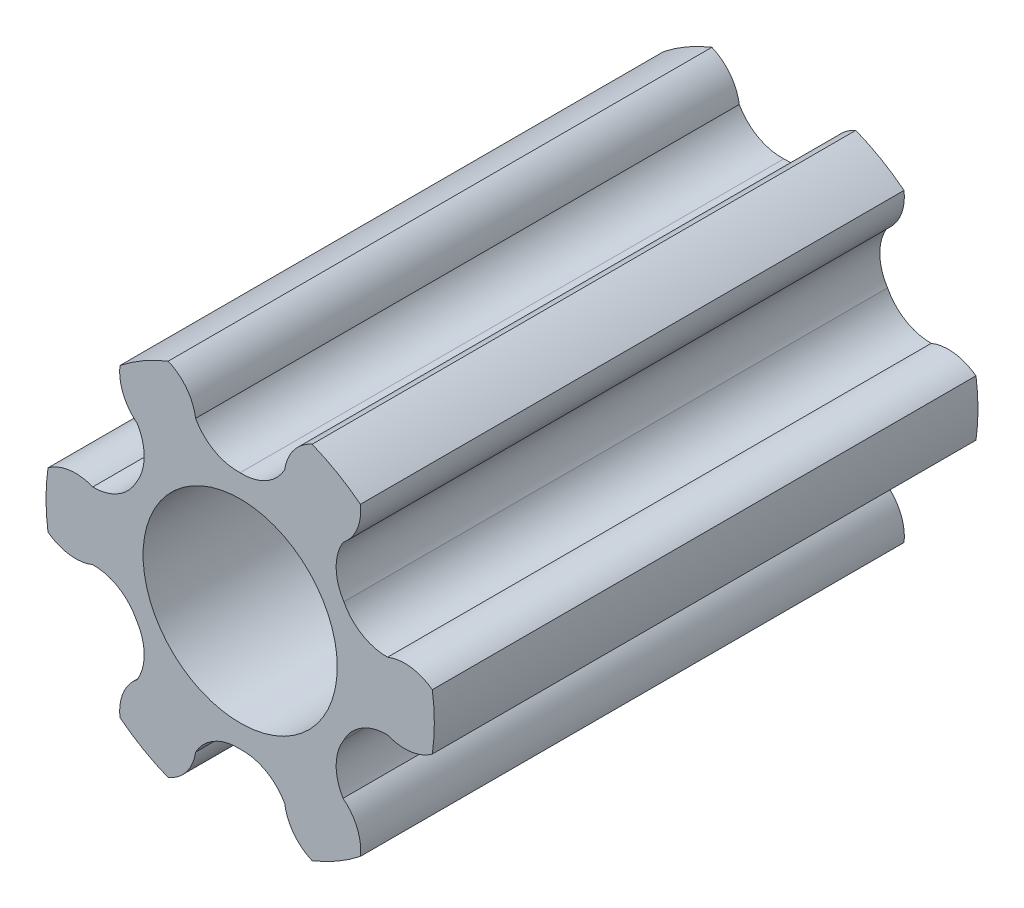
SolidWorks part; units mm, degrees
ref_plane "Front Plane" through (0, 0, 0) normal (0, 0, 1) x (1, 0, 0)
ref_plane "Top Plane" through (0, 0, 0) normal (0, 1, 0) x (1, 0, 0)
ref_plane "Right Plane" through (0, 0, 0) normal (1, 0, 0) x (0, 0, -1)
sketch "Sketch1" plane through (0, 0, 0) normal (0, 0, 1) x (1, 0, 0)
  line L1 (3.5355, -3.5355) -> (-3.5355, -3.5355) construction
  line L2 (3.5355, -3.5355) -> (3.5355, 3.5355) construction
  line L3 (3.5355, 3.5355) -> (-3.5355, 3.5355) construction
  line L4 (-3.5355, -3.5355) -> (-3.5355, 3.5355) construction
  line L5 (3.5355, -3.5355) -> (-3.5355, 3.5355) construction
  line L6 (3.5355, 3.5355) -> (-3.5355, -3.5355) construction
  circle A0 centre (0, 0) radius 10
  circle A1 centre (0, 0) radius 5
  dimension "D1" = 20
  dimension "D2" = 10
extrude "Boss-Extrude1" add sketch "Sketch1" along normal blind 28
sketch "Sketch2" plane through (0, 0, 0) normal (0, 0, 1) x (1, 0, 0)
  line L0 (0, 0) -> (0, 13.1096) construction
  arc A4 (-5.7202, 9.2219) -> (-2.2947, 7.4428) centre (-4.6421, 7.1104) cw
  arc A5 (-2.2947, 7.4428) -> (0, 6.1656) centre (-0.1244, 8.642) ccw
  arc A6 (-5.7202, 9.2219) -> (0, 13.1096) centre (4.1982, 0.7803) cw
  arc A7 (5.7202, 9.2219) -> (0, 13.1096) centre (-4.1982, 0.7803) ccw
  arc A8 (2.2947, 7.4428) -> (0, 6.1656) centre (0.1244, 8.642) cw
  arc A9 (5.7202, 9.2219) -> (2.2947, 7.4428) centre (4.6421, 7.1104) ccw
  point P15 (-1.981, 7.3762)
  point P16 (-5.7202, 9.2219)
extrude "Cut-Extrude1" cut sketch "Sketch2" along normal through all
pattern_circular "CirPattern1" count 6 over 360 about axis through (0, 0, 28) along (0, 0, -1) of "Cut-Extrude1" reverse direction yes
